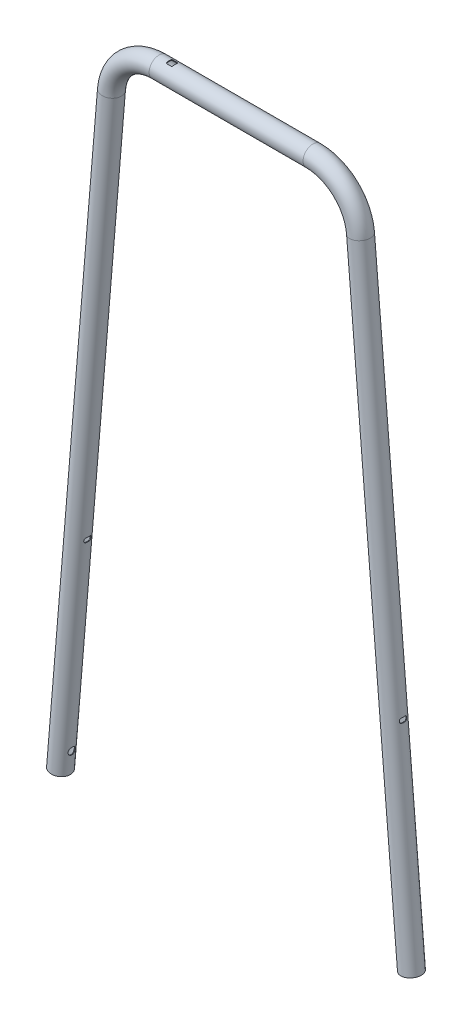
SolidWorks part; units mm, degrees
ref_plane "Front Plane" through (0, 0, 0) normal (0, 0, 1) x (1, 0, 0)
ref_plane "Top Plane" through (0, 0, 0) normal (0, 1, 0) x (1, 0, 0)
ref_plane "Right Plane" through (0, 0, 0) normal (1, 0, 0) x (0, 0, -1)
sketch "Sketch1" plane through (0, 0, 0) normal (0, 0, 1) x (1, 0, 0)
  line L0 (0, 0) -> (0, 595.2821) construction
  line L1 (0, 0) -> (414.971, 0) construction
  line L2 (-85.4711, 567.016) -> (85.4711, 567.016)
  line L3 (138.2891, 518.4048) -> (194.85, -162.284)
  line L4 (-138.2891, 518.4048) -> (-194.85, -162.284)
  line L5 (-194.85, -162.284) -> (-299.6948, -162.284) construction
  arc A0 (138.2891, 518.4048) -> (85.4711, 567.016) centre (85.4711, 514.016) ccw
  arc A1 (-138.2891, 518.4048) -> (-85.4711, 567.016) centre (-85.4711, 514.016) cw
  point P12 (134.2498, 567.016)
  point P17 (0, 567.016)
  dimension "D4" = 53
  dimension "D1" = 389.7
  dimension "D2" = 9.5
  dimension "D3" = 729.3
ref_plane "Plane1" through (-194.85, -162.284, 0) normal (-0.0828, -0.9966, 0) x (-0.9966, 0.0828, 0)
sketch "Sketch2" plane through (-194.85, -162.284, 0) normal (-0.0828, -0.9966, 0) x (-0.9966, 0.0828, 0)
  circle A0 centre (0, 0) radius 11
  circle A1 centre (0, 0) radius 10.2
  dimension "D1" = 0.8
sweep "Sweep2" add profiles "Sketch2" path "Sketch1"
sketch "Sketch6" plane through (-14.7284, -177.251, 0) normal (-0.0828, -0.9966, 0) x (0.9966, -0.0828, 0)
  line L0 (-180.7423, 0) -> (-190.9423, 0)
  line L1 (-180.7423, 0) -> (-180.7423, 10.2)
  circle A0 centre (-180.7423, 0) radius 10.2 construction
  circle A1 centre (-180.7423, 0) radius 10.2 construction
ref_plane "Plane3" through (-194.85, -162.284, 0) normal (-0.9966, 0.0828, 0) x (0, 0, 1)
ref_plane "Plane4" through (0, 578.016, 0) normal (0, 1, 0) x (1, 0, 0)
sketch "Sketch17" plane through (-194.85, -162.284, 0) normal (-0.9966, 0.0828, 0) x (0, 0, 1)
  line L0 (0, 0) -> (0, 23.8) construction
  line L1 (-11, 0) -> (11, 0) construction
  line L2 (0, 23.8) -> (0, 236.8) construction
  circle A0 centre (0, 23.8) radius 4
  dimension "D3" = 8
  dimension "D1" = 23.8
  dimension "D2" = 236.8
extrude "Cut-Extrude6" cut sketch "Sketch17" against normal blind 50
sketch "Sketch18" plane through (-194.85, -162.284, 0) normal (-0.9966, 0.0828, 0) x (0, 0, 1)
  line L0 (0, 0) -> (0, 236.8) construction
  line L1 (-10.2, 0) -> (10.2, 0) construction
  line L3 (-2, 239.3) -> (2, 239.3)
  line L4 (-4, 237.3) -> (-4, 236.3)
  line L5 (-2, 234.3) -> (2, 234.3)
  line L6 (4, 237.3) -> (4, 236.3)
  line L7 (-4, 239.3) -> (4, 234.3) construction
  line L8 (-4, 234.3) -> (4, 239.3) construction
  arc A0 (-2, 234.3) -> (-4, 236.3) centre (-2, 236.3) cw
  arc A1 (4, 236.3) -> (2, 234.3) centre (2, 236.3) cw
  arc A2 (2, 239.3) -> (4, 237.3) centre (2, 237.3) cw
  arc A3 (-2, 239.3) -> (-4, 237.3) centre (-2, 237.3) ccw
  dimension "D3" = 2
  dimension "D1" = 5
  dimension "D2" = 8
  dimension "D4" = 236.8
extrude "Cut-Extrude7" cut sketch "Sketch18" against normal blind 50 and the other way blind 50
mirror "Mirror2" about plane through (0, 0, 0) normal (1, 0, 0) of "Cut-Extrude6", "Cut-Extrude7"
sketch "Sketch19" plane through (-194.85, -162.284, 0) normal (-0.9966, 0.0828, 0) x (0, 0, 1)
  line L0 (0, 0) -> (0, 496.8) construction
  line L1 (-10.2, 0) -> (10.2, 0) construction
  circle A0 centre (0, 496.8) radius 4
  dimension "D1" = 496.8
extrude "Cut-Extrude8" cut sketch "Sketch19" along normal blind 50
sketch "Sketch20" plane through (0, 578.016, 0) normal (0, 1, 0) x (1, 0, 0)
  line L0 (-205.8122, 0) -> (-70.9891, 0) construction
  circle A0 centre (-70.9891, 0) radius 3.5
  ellipse E0 centre (-194.85, 0) end of major axis (-194.85, 11) minor radius 10.9622 construction
  ellipse E1 centre (-138.2891, 0) end of major axis (-138.2891, 11) minor radius 10.9622 construction
  dimension "D2" = 7
  dimension "D1" = 67.3
extrude "Cut-Extrude9" cut sketch "Sketch20" against normal blind 50
sketch "Sketch21" plane through (0, 578.016, 0) normal (0, 1, 0) x (1, 0, 0)
  line L0 (-205.8122, 0) -> (-70.9891, 0) construction
  line L2 (-73.4891, -3.5) -> (-68.4891, -3.5)
  line L3 (-74.4891, -2.5) -> (-74.4891, 2.5)
  line L4 (-73.4891, 3.5) -> (-68.4891, 3.5)
  line L5 (-67.4891, -2.5) -> (-67.4891, 2.5)
  line L6 (-74.4891, -3.5) -> (-67.4891, 3.5) construction
  line L7 (-74.4891, 3.5) -> (-67.4891, -3.5) construction
  arc A0 (-73.4891, 3.5) -> (-74.4891, 2.5) centre (-73.4891, 2.5) ccw
  arc A1 (-74.4891, -2.5) -> (-73.4891, -3.5) centre (-73.4891, -2.5) ccw
  arc A2 (-68.4891, 3.5) -> (-67.4891, 2.5) centre (-68.4891, 2.5) cw
  arc A3 (-67.4891, -2.5) -> (-68.4891, -3.5) centre (-68.4891, -2.5) cw
  ellipse E0 centre (-194.85, 0) end of major axis (-194.85, 11) minor radius 10.9622 construction
  dimension "D3" = 1
  dimension "D4" = 1
  dimension "D1" = 7
  dimension "D2" = 7
extrude "Cut-Extrude10" cut sketch "Sketch21" against normal blind 10
